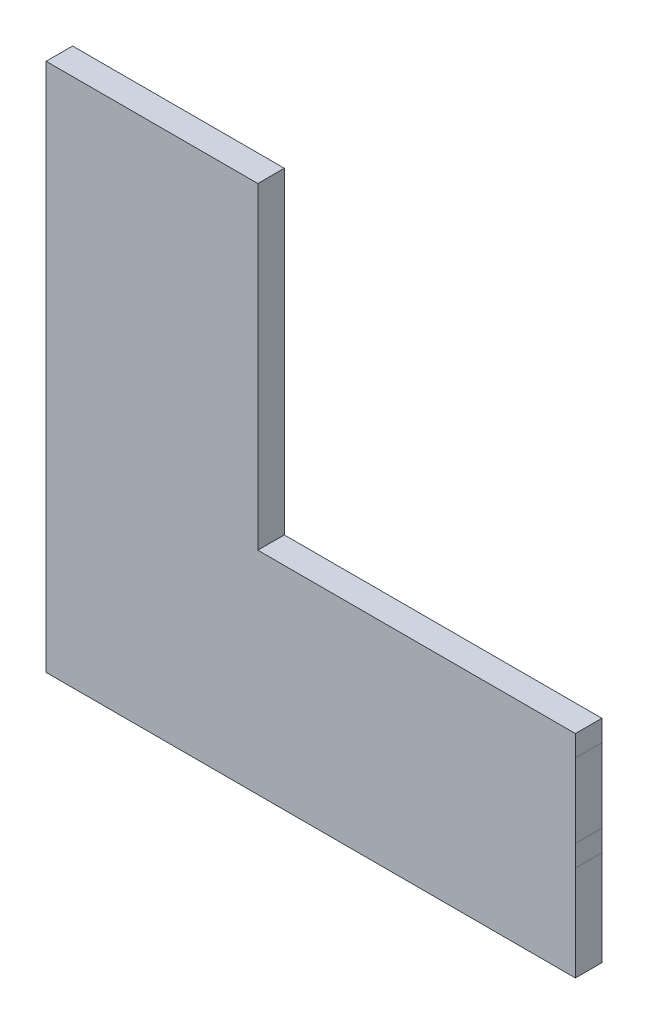
SolidWorks part; units mm, degrees
ref_plane "Front Plane" through (0, 0, 0) normal (0, 0, 1) x (1, 0, 0)
ref_plane "Top Plane" through (0, 0, 0) normal (0, 1, 0) x (1, 0, 0)
ref_plane "Right Plane" through (0, 0, 0) normal (1, 0, 0) x (0, 0, -1)
sketch "Sketch1" plane through (0, 0, 0) normal (0, 0, 1) x (1, 0, 0)
  line L0 (0, 0) -> (1000, 0)
  line L1 (1000, 0) -> (1000, 400)
  line L2 (1000, 400) -> (400, 400)
  line L3 (400, 400) -> (400, 1000)
  line L4 (400, 1000) -> (0, 1000)
  line L5 (0, 1000) -> (0, 0)
  dimension "D1" = 1000
  dimension "D2" = 600
  dimension "D3" = 400
  dimension "D4" = 1000
extrude "Boss-Extrude1" add sketch "Sketch1" along normal blind 50
sketch "Sketch3" plane through (1000, 0, 0) normal (1, 0, 0) x (0, 0, -1)
  line L0 (-50, 360) -> (0, 360)
  line L1 (-50, 0) -> (-50, 400) construction
  line L2 (0, 0) -> (0, 400) construction
  line L3 (-50, 400) -> (0, 400) construction
  line L4 (-50, 220) -> (0, 220)
  line L5 (-50, 180) -> (0, 180)
  line L6 (-50, 0) -> (0, 0) construction
  dimension "D1" = 40
  dimension "D2" = 40
  dimension "D3" = 180
split line "Split Line1"
